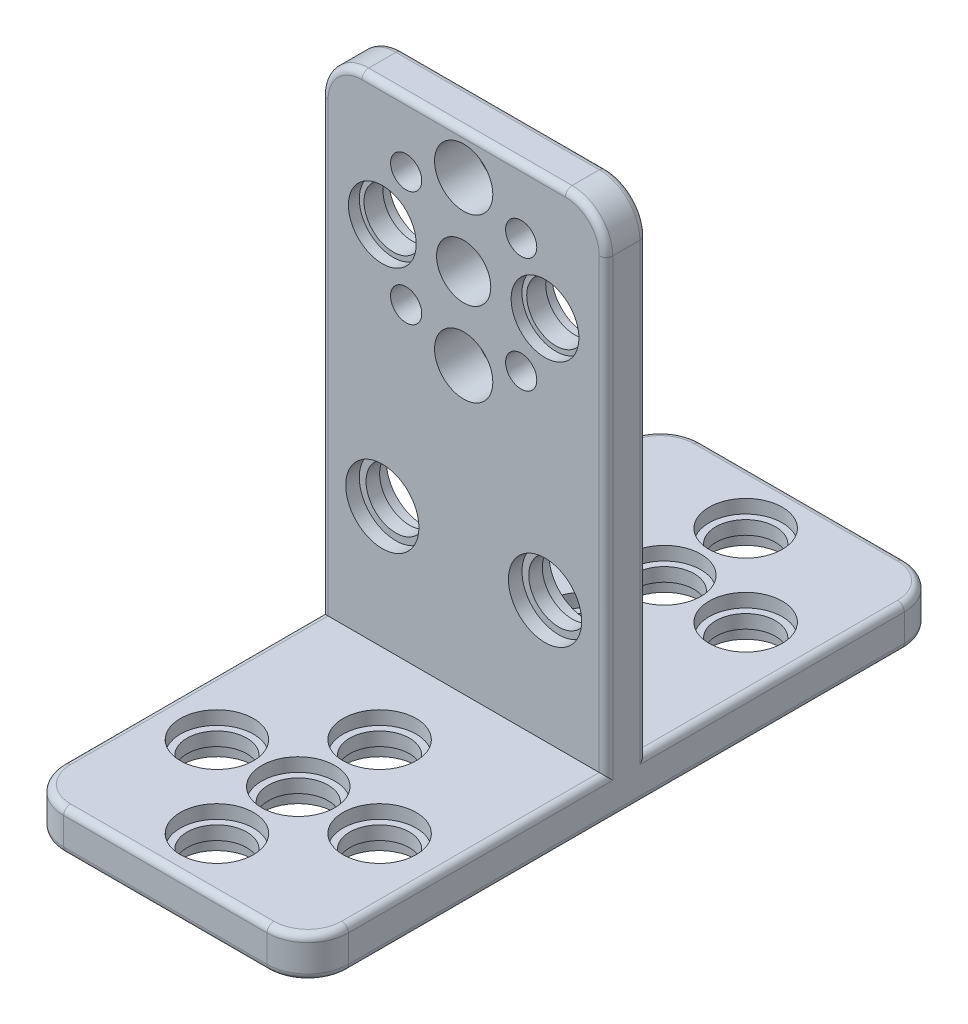
SolidWorks part; units mm, degrees
material "ABS"
ref_plane "Front Plane" through (0, 0, 0) normal (0, 0, 1) x (1, 0, 0)
ref_plane "Top Plane" through (0, 0, 0) normal (0, 1, 0) x (1, 0, 0)
ref_plane "Right Plane" through (0, 0, 0) normal (1, 0, 0) x (0, 0, -1)
sketch "Sketch1" plane through (0, 0, 0) normal (0, 0, 1) x (1, 0, 0)
  line L0 (-6.9141, 9) -> (6.9141, 9) construction
  line L1 (10.5, -27) -> (-10.5, -27)
  line L2 (10.5, -27) -> (10.5, 9)
  line L3 (10.5, 9) -> (-10.5, 9)
  line L4 (-10.5, -27) -> (-10.5, 9)
  line L5 (-10.5, 5.1503) -> (-10.5, -23.1503) construction
  line L6 (10.5, -23.1503) -> (10.5, 5.1503) construction
  line L7 (6.9141, -27) -> (-6.9141, -27) construction
  circle A0 centre (-6, 0) radius 2.15
  circle A1 centre (0, 6) radius 2.15
  circle A2 centre (0, 0) radius 2
  circle A3 centre (6, 0) radius 2.15
  circle A4 centre (0, -6) radius 2.15
  dimension "D1" = 4
  dimension "D2" = 4.3
extrude "Boss-Extrude1" add sketch "Sketch1" along normal blind 3
sketch "Sketch2" plane through (0, 0, 3) normal (0, 0, 1) x (1, 0, 0)
  circle A0 centre (-6, 0) radius 2.65
  circle A1 centre (0, 6) radius 2.65
  circle A2 centre (6, 0) radius 2.65
  circle A3 centre (0, -6) radius 2.65
  circle A4 centre (0, 0) radius 2.5
  dimension "D1" = 5.3
  dimension "D2" = 5
extrude "Cut-Extrude1" cut sketch "Sketch2" against normal blind 0.8
fillet "Fillet1" [suppressed] radius 2
sketch "Sketch5" plane through (0, -27, 0) normal (0, -1, 0) x (1, 0, 0)
  line L0 (-10.5, 3) -> (-10.5, 0) construction
  line L1 (10.5, 0) -> (-10.5, 0)
  line L2 (10.5, 0) -> (10.5, 25)
  line L3 (10.5, 25) -> (-10.5, 25)
  line L4 (-10.5, 0) -> (-10.5, 25)
  dimension "D1" = 25
extrude "Boss-Extrude2" add sketch "Sketch5" along normal blind 3
sketch "Sketch6" plane through (0, -30, 0) normal (0, -1, 0) x (1, 0, 0)
  point P0 (-0.2, 21)
  point P1 (5.8, 15)
  point P2 (-0.2, 9)
  point P3 (-6.2, 15)
  point P4 (-0.2, 15)
hole_wizard "Hole1" positions "Sketch8" profile "Sketch7" legacy end condition up to next
sketch "Sketch8" plane through (0, -30, 0) normal (0, -1, 0) x (-1, 0, 0)
  point P0 (0.2, -21)
  point P3 (6.2, -15)
  point P6 (0.2, -15)
  point P9 (-5.8, -15)
  point P12 (0.2, -9)
sketch "Sketch7" plane through (-0.2, -30, 21) normal (1, 0, 0) x (0, 0, -1)
  line L0 (0, 0) -> (0, 3)
  line L1 (0, 3) -> (2.2, 3)
  line L2 (2.2, 3) -> (2.2, 1)
  line L3 (2.2, 1) -> (2.7, 1)
  line L4 (2.7, 1) -> (2.7, 0)
  line L5 (2.7, 0) -> (0, 0)
  line L6 (0, 110) -> (0, -10) construction
  dimension "Diameter" = 4.4
  dimension "Depth" = 3
  dimension "C-Bore Diameter" = 5.4
  dimension "C-Bore Depth" = 1
sketch "Sketch9" plane through (0, 0, 3) normal (0, 0, 1) x (1, 0, 0)
  line L0 (0, 0) -> (0, 6) construction
  line L1 (0, 0) -> (-4.2426, 4.2426) construction
  circle A0 centre (0, 0) radius 6 construction
  point P4 (-4.2426, 4.2426)
  point P5 (-4.2426, -4.2426)
  point P6 (4.2426, -4.2426)
  point P7 (4.2426, 4.2426)
  dimension "D1" = 45
hole_wizard "CBORE for M1.6 Hex Socket Head Cap Screw1" positions "Sketch11" profile "Sketch10" counterbore size "M1.6" standard "ISO" end condition up to next
sketch "Sketch11" plane through (0, 0, 3) normal (0, 0, 1) x (1, 0, 0)
  point P0 (-4.2426, 4.2426)
  point P3 (-4.2426, -4.2426)
  point P6 (4.2426, -4.2426)
  point P9 (4.2426, 4.2426)
sketch "Sketch10" plane through (-4.2426, 4.2426, 3) normal (1, 0, 0) x (0, -1, 0)
  line L0 (0, 0) -> (0, 3)
  line L1 (0, 3) -> (1.15, 3)
  line L3 (1.15, 3) -> (1.15, 1)
  line L4 (1.15, 1) -> (2, 1)
  line L5 (2, 1) -> (2, 0)
  line L7 (2, 0) -> (0, 0)
  line L11 (0, -6.35) -> (0, 107.95) construction
  dimension "Thru Hole Dia." = 2.3
  dimension "Thru Hole Depth" = 3
  dimension "C'Bore Dia." = 4
  dimension "C'Bore Depth" = 1
hole_wizard "Hole2" positions "Sketch13" profile "Sketch12" legacy
sketch "Sketch13" plane through (1.5939, -9.4748, 0) normal (0, 0, 1) x (1, 0, 0)
  line L0 (-1.5939, 9.4748) -> (-1.5939, -8.5252) construction
  line L1 (-1.5939, -8.5252) -> (-7.5939, -8.5252) construction
  point P0 (4.4061, -8.5252)
  point P2 (-7.5939, -8.5252)
  dimension "D1" = 18
  dimension "D2" = 12
sketch "Sketch12" plane through (6, -18, 0) normal (1, 0, 0) x (0, 1, 0)
  line L0 (0, 0) -> (0, 100)
  line L1 (0, 100) -> (2.2, 100)
  line L2 (2.2, 100) -> (2.2, 1)
  line L3 (2.2, 1) -> (2.7, 1)
  line L4 (2.7, 1) -> (2.7, 0)
  line L5 (2.7, 0) -> (0, 0)
  line L6 (0, 110) -> (0, -10) construction
  dimension "Diameter" = 4.4
  dimension "Depth" = 100
  dimension "C-Bore Diameter" = 5.4
  dimension "C-Bore Depth" = 1
sketch "Sketch15" plane through (0, 0, 0) normal (0, 0, -1) x (-1, 0, 0)
  circle A0 centre (-6, 0) radius 2.5
  circle A1 centre (6, 0) radius 2.5
  dimension "D1" = 5
extrude "Cut-Extrude2" cut sketch "Sketch15" against normal blind 0.8
hole_wizard "Hole3" positions "Sketch17" profile "Sketch16" legacy
sketch "Sketch17" plane through (0, 0, 3) normal (0, 0, 1) x (1, 0, 0)
  point P0 (-6, -18)
  point P3 (6, -18)
sketch "Sketch16" plane through (-6, -18, 3) normal (1, 0, 0) x (0, -1, 0)
  line L0 (0, 0) -> (0, 100)
  line L1 (0, 100) -> (2.2, 100)
  line L2 (2.2, 100) -> (2.2, 1)
  line L3 (2.2, 1) -> (2.7, 1)
  line L4 (2.7, 1) -> (2.7, 0)
  line L5 (2.7, 0) -> (0, 0)
  line L6 (0, 110) -> (0, -10) construction
  dimension "Diameter" = 4.4
  dimension "Depth" = 100
  dimension "C-Bore Diameter" = 5.4
  dimension "C-Bore Depth" = 1
hole_wizard "Hole4" positions "Sketch19" profile "Sketch18" legacy
sketch "Sketch19" plane through (0, -27, 0) normal (0, 1, 0) x (1, 0, 0)
  point P0 (-0.2, -21)
  point P3 (-6.2, -15)
  point P6 (-0.2, -15)
  point P9 (5.8, -15)
  point P12 (-0.2, -9)
sketch "Sketch18" plane through (-0.2, -27, 21) normal (1, 0, 0) x (0, 0, 1)
  line L0 (0, 0) -> (0, 100)
  line L1 (0, 100) -> (2.2, 100)
  line L2 (2.2, 100) -> (2.2, 1)
  line L3 (2.2, 1) -> (2.7, 1)
  line L4 (2.7, 1) -> (2.7, 0)
  line L5 (2.7, 0) -> (0, 0)
  line L6 (0, 110) -> (0, -10) construction
  dimension "Diameter" = 4.4
  dimension "Depth" = 100
  dimension "C-Bore Diameter" = 5.4
  dimension "C-Bore Depth" = 1
ref_plane "Plane1" through (0, 0, 1.5) normal (0, 0, 1) x (1, 0, 0)
fillet "Fillet2" [suppressed] radius 3
fillet "Fillet3" [suppressed] radius 0.5
fillet "Fillet4" radius 3 4 edges at (10.5, -28.5, 25) (-10.5, -28.5, 25) (-10.5, 9, 1.5) (10.5, 9, 1.5)
fillet "Fillet5" radius 0.5 20 edges at (0, -27, 25) (10.5, -30, 11) (0, -30, 25) (-10.5, -30, 11) (-10.5, -12, 0) (0, 9, 0) (0, 9, 3) (10.5, -12, 0) (9.6213, -27, 24.1213) (9.6213, -30, 24.1213) (-9.6213, -27, 24.1213) (-9.6213, -30, 24.1213) (-9.6213, 8.1213, 3) (-9.6213, 8.1213, 0) (9.6213, 8.1213, 3) (9.6213, 8.1213, 0)
mirror "Mirror1" about plane through (0, 0, 1.5) normal (0, 0, 1) of bodies 110 107
